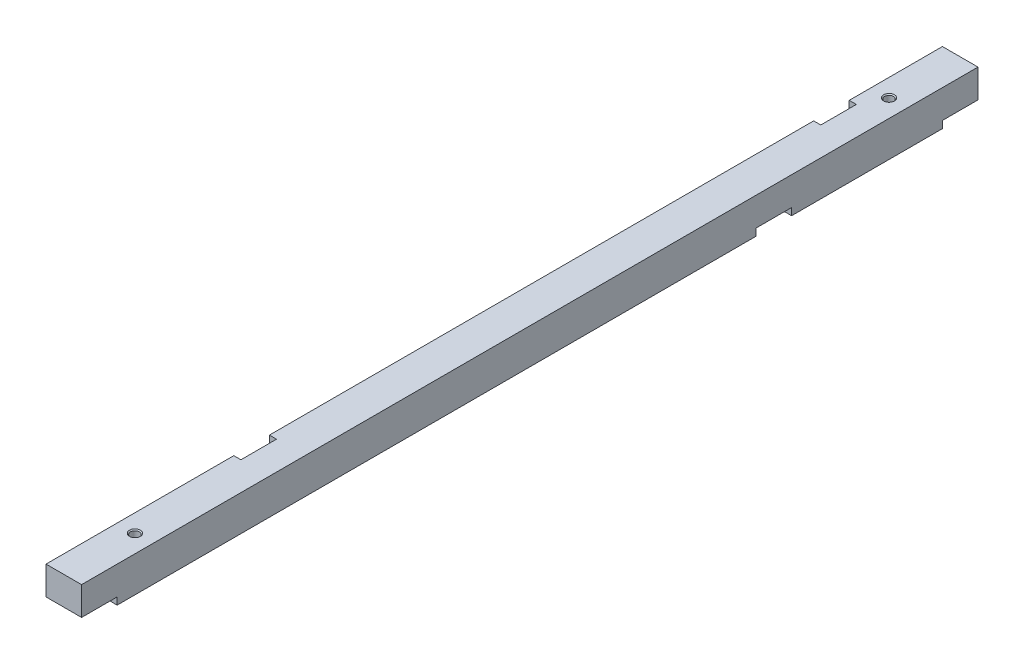
SolidWorks part; units mm, degrees
ref_plane "Plan de face" through (0, 0, 0) normal (0, 0, 1) x (1, 0, 0)
ref_plane "Plan de dessus" through (0, 0, 0) normal (0, 1, 0) x (1, 0, 0)
ref_plane "Plan de droite" through (0, 0, 0) normal (1, 0, 0) x (0, 0, -1)
sketch "Esquisse1" plane through (0, 0, 0) normal (0, 0, 1) x (1, 0, 0)
  line L0 (-5, 5) -> (5, -5) construction
  line L1 (-5, 5) -> (5, 5)
  line L2 (-5, 5) -> (-5, -5)
  line L3 (-5, -5) -> (5, -5)
  line L4 (5, 5) -> (5, -5)
  dimension "D1" = 10
extrude "Boss.-Extru.1" add sketch "Esquisse1" along normal blind 252
sketch "Esquisse2" plane through (-5, 0, 0) normal (-1, 0, 0) x (0, 0, 1)
  line L0 (0, -3) -> (0, -303) construction
  line L1 (0, -5) -> (10, -5)
  line L2 (0, -5) -> (0, -3)
  line L3 (0, -3) -> (10, -3)
  line L4 (10, -5) -> (10, -3)
  line L5 (10, -3) -> (10, -170) construction
  line L6 (52.4, -3) -> (52.4, -170) construction
  line L7 (52.4, -5) -> (62.4, -5)
  line L8 (52.4, -5) -> (52.4, -3)
  line L9 (52.4, -3) -> (62.4, -3)
  line L10 (62.4, -5) -> (62.4, -3)
  line L11 (62.4, -3) -> (62.4, -170) construction
  line L12 (242, -3) -> (242, -170) construction
  line L13 (242, -5) -> (252, -5)
  line L14 (242, -5) -> (242, -3)
  line L15 (242, -3) -> (252, -3)
  line L16 (252, -5) -> (252, -3)
  line L17 (252, -3) -> (252, -297.8) construction
  line L18 (252, -5) -> (0, -5) construction
  dimension "D1" = 2
extrude "Enlèv. mat.-Extru.1" cut sketch "Esquisse2" against normal through all
sketch "Esquisse3" plane through (0, -5, 0) normal (0, -1, 0) x (1, 0, 0)
  line L4 (3, 36.2) -> (3, 26.2)
  line L5 (224, 36.2) -> (3, 36.2)
  line L6 (224, 26.2) -> (224, 36.2)
  line L7 (3, 26.2) -> (224, 26.2)
  line L8 (3, 36.2) -> (3, 26.2)
  line L9 (224, 36.2) -> (3, 36.2)
  line L10 (224, 26.2) -> (224, 36.2)
  line L11 (3, 26.2) -> (224, 26.2)
  dimension "D1" = 0
extrude "Enlèv. mat.-Extru.2" [suppressed] cut sketch "Esquisse3" against normal through all
sketch "Esquisse4" plane through (0, 5, 0) normal (0, 1, 0) x (1, 0, 0)
  line L4 (3, -189.2) -> (3, -199.2)
  line L5 (3, -199.2) -> (224, -199.2)
  line L6 (224, -199.2) -> (224, -189.2)
  line L7 (224, -189.2) -> (3, -189.2)
  line L8 (3, -189.2) -> (3, -199.2)
  line L9 (3, -199.2) -> (224, -199.2)
  line L10 (224, -199.2) -> (224, -189.2)
  line L11 (224, -189.2) -> (3, -189.2)
  dimension "D1" = 0
extrude "Enlèv. mat.-Extru.3" [suppressed] cut sketch "Esquisse4" against normal through all
sketch "Esquisse5" plane through (0, 5, 0) normal (0, 1, 0) x (1, 0, 0)
  line L0 (3, -199.2) -> (224, -199.2) construction
  line L1 (-5, -199.2) -> (-3, -199.2)
  line L2 (-5, -199.2) -> (-5, -189.2)
  line L3 (-5, -189.2) -> (-3, -189.2)
  line L4 (-3, -199.2) -> (-3, -189.2)
  line L5 (3, -189.2) -> (224, -189.2) construction
  line L6 (3, -36.2) -> (224, -36.2) construction
  line L7 (-5, -36.2) -> (-3, -36.2)
  line L8 (-5, -36.2) -> (-5, -26.2)
  line L9 (-5, -26.2) -> (-3, -26.2)
  line L10 (-3, -36.2) -> (-3, -26.2)
  line L11 (3, -26.2) -> (224, -26.2) construction
  line L12 (-5, -252) -> (-5, 0) construction
  dimension "D1" = 2
extrude "Enlèv. mat.-Extru.4" cut sketch "Esquisse5" against normal through all
hole_wizard "Trou taraudé M3x0.51" positions "Esquisse7" profile "Esquisse6" tap size "M3x0.5" standard "Ansi Metric" end condition through all
sketch "Esquisse7" plane through (0, 5, 0) normal (0, 1, 0) x (1, 0, 0)
  point P0 (0, -20)
  point P3 (0, -232)
sketch "Esquisse6" plane through (0, 5, 20) normal (1, 0, 0) x (0, 0, 1)
  line L0 (0, 0) -> (0, 10)
  line L1 (0, 10) -> (1.25, 10)
  line L2 (1.25, 10) -> (1.25, 0.275)
  line L3 (1.25, 0.275) -> (1.525, 0)
  line L5 (1.525, 0) -> (0, 0)
  line L6 (-1.25, 0.275) -> (-1.525, 0) construction
  line L11 (0, -6.35) -> (0, 107.95) construction
  dimension "Diamètre du trou pour taraudage jusqu'au prochain" = 2.5
  dimension "Profondeur du trou pour taraudage jusqu'au prochain" = 10
  dimension "Diamètre du fraisage entrant" = 3.05
  dimension "Angle du fraisage entrant" = 90
cosmetic thread "Filetage de perçage1" parameters "D2"=3
cosmetic thread "Filetage de perçage2" parameters "D2"=3
